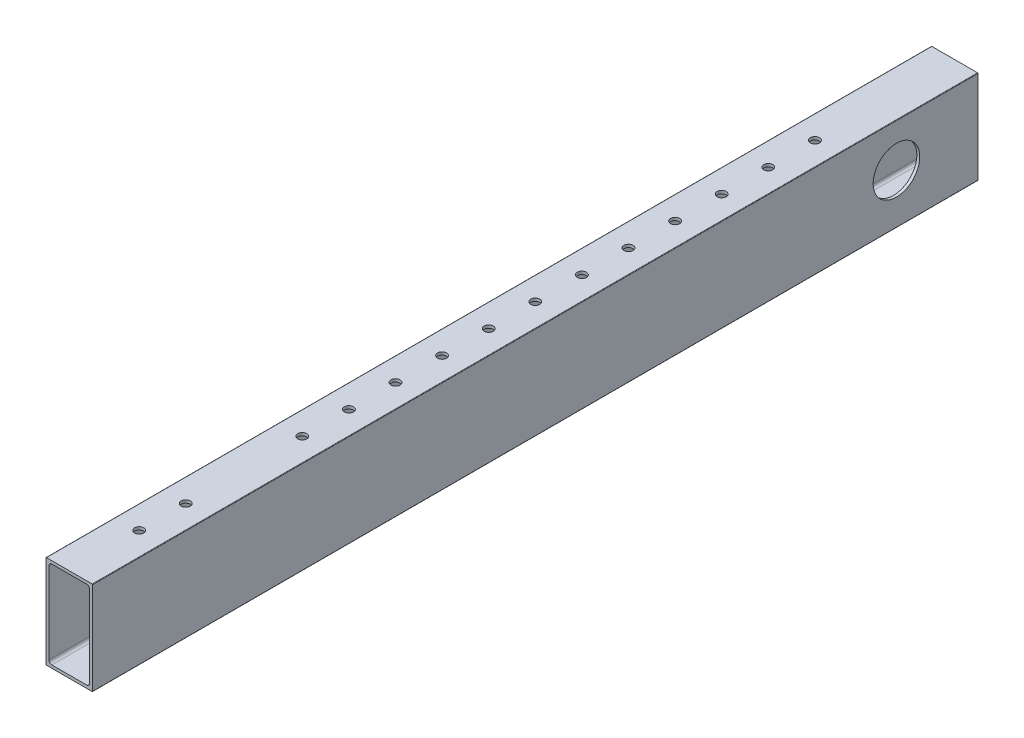
SolidWorks part; units mm, degrees
material "6061 Alloy"
ref_plane "Front Plane" through (0, 0, 0) normal (0, 0, 1) x (1, 0, 0)
ref_plane "Top Plane" through (0, 0, 0) normal (0, 1, 0) x (1, 0, 0)
ref_plane "Right Plane" through (0, 0, 0) normal (1, 0, 0) x (0, 0, -1)
ref_plane "Plane1" through (0, 0, 0) normal (0, 0, -1) x (-1, 0, 0)
sketch "Sketch1" plane through (0, 0, 0) normal (0, 0, -1) x (-1, 0, 0)
  line L0 (-11.1125, -22.225) -> (-11.1125, 22.225)
  line L1 (-9.525, 23.8125) -> (9.525, 23.8125)
  line L2 (11.1125, 22.225) -> (11.1125, -22.225)
  line L3 (9.525, -23.8125) -> (-9.525, -23.8125)
  line L4 (-12.7, 25.146) -> (-12.7, -25.146)
  line L5 (-12.446, -25.4) -> (12.446, -25.4)
  line L6 (12.7, -25.146) -> (12.7, 25.146)
  line L7 (12.446, 25.4) -> (-12.446, 25.4)
  arc A0 (-11.1125, 22.225) -> (-9.525, 23.8125) centre (-9.525, 22.225) cw
  arc A1 (9.525, 23.8125) -> (11.1125, 22.225) centre (9.525, 22.225) cw
  arc A2 (11.1125, -22.225) -> (9.525, -23.8125) centre (9.525, -22.225) cw
  arc A3 (-9.525, -23.8125) -> (-11.1125, -22.225) centre (-9.525, -22.225) cw
  arc A4 (-12.7, -25.146) -> (-12.446, -25.4) centre (-12.446, -25.146) ccw
  arc A5 (12.446, -25.4) -> (12.7, -25.146) centre (12.446, -25.146) ccw
  arc A6 (12.7, 25.146) -> (12.446, 25.4) centre (12.446, 25.146) ccw
  arc A7 (-12.446, 25.4) -> (-12.7, 25.146) centre (-12.446, 25.146) ccw
extrude "Boss-Extrude1" add sketch "Sketch1" against normal blind 457.2 and the other way blind 25.4
sketch "Sketch2" plane through (-12.7, 0, 0) normal (-1, 0, 0) x (0, 0, 1)
  line L0 (0, 1.778) -> (19.05, 1.778) construction
  line L1 (0, 25.146) -> (0, -25.146) construction
  line L8 (-25.4, 25.146) -> (457.2, 25.146) construction
  line L9 (-25.4, -25.146) -> (457.2, -25.146) construction
  line L10 (-25.4, -25.4) -> (457.2, -25.4) construction
  circle A0 centre (19.05, 1.778) radius 12.7
  dimension "D3" = 27.178
  dimension "D2" = 25.4
  dimension "D1" = 19.05
extrude "Cut-Extrude1" cut sketch "Sketch2" against normal blind 25.4
sketch "Sketch3" plane through (0, -25.4, 0) normal (0, -1, 0) x (1, 0, 0)
  line L0 (0, 0) -> (0, 457.2) construction
  line L1 (12.446, 457.2) -> (-12.446, 457.2) construction
  line L2 (12.446, -25.4) -> (-12.446, -25.4) construction
  line L3 (-12.7, 355.6) -> (12.7, 355.6) construction
  line L4 (-12.7, 457.2) -> (-12.7, -25.4) construction
  line L5 (12.7, 457.2) -> (12.7, -25.4) construction
  circle A0 centre (0, 50.8) radius 2.4892
  circle A1 centre (0, 76.2) radius 2.4892
  circle A2 centre (0, 101.6) radius 2.4892
  circle A3 centre (0, 127) radius 2.4892
  circle A4 centre (0, 152.4) radius 2.4892
  circle A5 centre (0, 177.8) radius 2.4892
  circle A6 centre (0, 203.2) radius 2.4892
  circle A7 centre (0, 228.6) radius 2.4892
  circle A8 centre (0, 254) radius 2.4892
  circle A9 centre (0, 279.4) radius 2.4892
  circle A10 centre (0, 304.8) radius 2.4892
  circle A11 centre (0, 393.7) radius 2.4892
  circle A12 centre (0, 419.1) radius 2.4892
  circle A13 centre (0, 330.2) radius 2.4892
  dimension "D1" = 76.2
  dimension "D2" = 4.9784
  dimension "D3" = 12
  dimension "D4" = 25.4
  dimension "D5" = 38.1
extrude "Cut-Extrude2" cut sketch "Sketch3" against normal through all both
